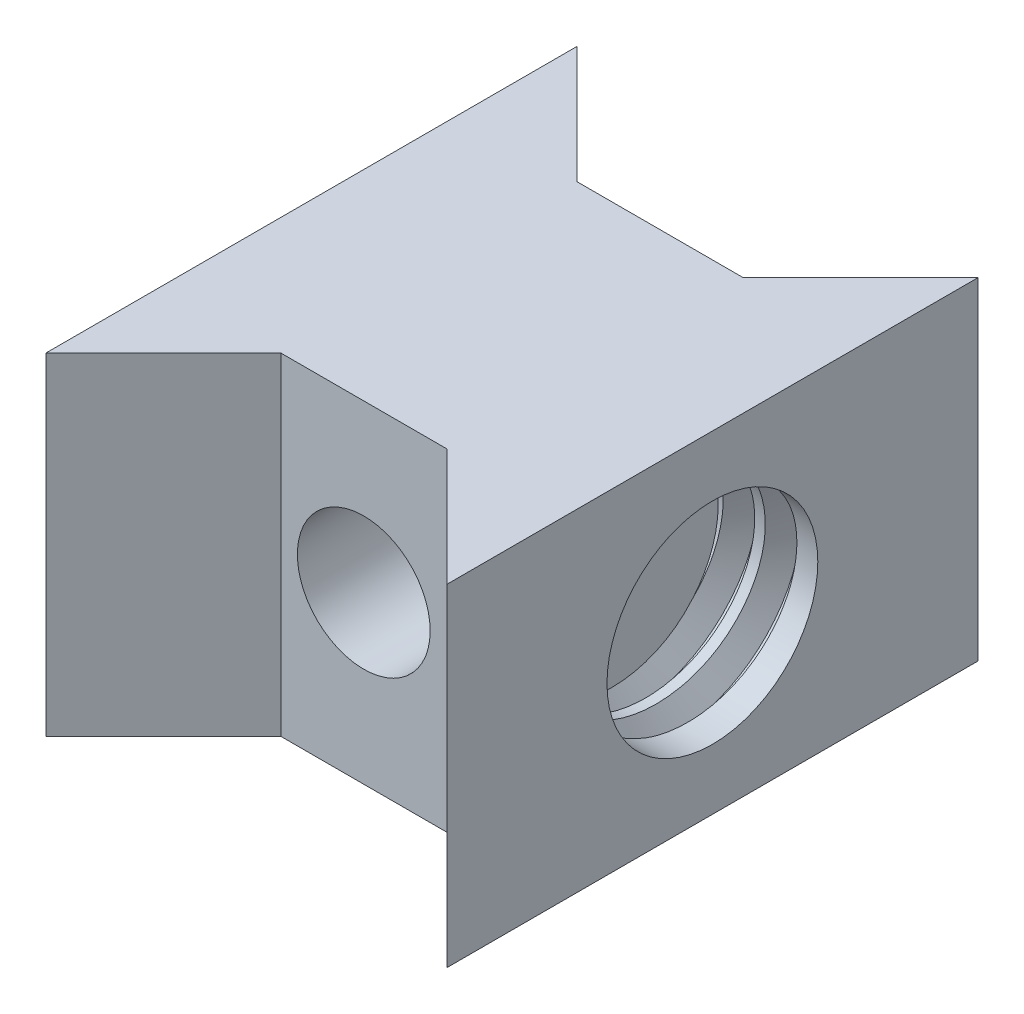
SolidWorks part; units mm, degrees
ref_plane "Front Plane" through (0, 0, 0) normal (0, 0, 1) x (1, 0, 0)
ref_plane "Top Plane" through (0, 0, 0) normal (0, 1, 0) x (1, 0, 0)
ref_plane "Right Plane" through (0, 0, 0) normal (1, 0, 0) x (0, 0, -1)
sketch "Sketch1" plane through (0, 0, 0) normal (0, 1, 0) x (1, 0, 0)
  line L0 (0, 0) -> (0, 8)
  line L1 (0, 0) -> (0, -8)
  line L2 (0, -8) -> (-3.5355, -4.4645)
  line L3 (0, 8) -> (-3.5355, 4.4645)
  line L5 (-3.5355, -4.4645) -> (-8.5355, -4.4645)
  line L6 (-3.5355, 4.4645) -> (-8.5355, 4.4645)
  line L7 (-8.5355, 4.4645) -> (-12.0711, 8)
  line L8 (-12.0711, 8) -> (-12.0711, -8)
  line L9 (-12.0711, -8) -> (-8.5355, -4.4645)
extrude "Boss-Extrude1" add sketch "Sketch1" along normal blind 10
sketch "Sketch3" plane through (0, 0, 0) normal (1, 0, 0) x (0, 0, -1)
  circle A0 centre (0, 5) radius 3.175
extrude "Cut-Extrude4" cut sketch "Sketch3" against normal blind 3
ref_plane "Plane4" through (-6.0355, 0, 0) normal (1, 0, 0) x (0, 0, -1)
mirror "Mirror2" about plane through (-6.0355, 0, 0) normal (1, 0, 0) of "Cut-Extrude4"
thread "Thread3" pitch 1.27 method cut profile "Thread Profile3" start angle 0, offset 0, length 3, pitch 1.27, diameter 6.35
ref_plane "Plane5" through (0, 5, 3.175) normal (0, -1, 0) x (0, 0, 1)
sketch "Thread Profile3" plane through (0, 5, 3.175) normal (0, -1, 0) x (0, 0, 1)
  line L0 (0, 0) -> (0, 1.27) construction
  line L1 (0, 0) -> (0.6874, 0.3969)
  line L2 (0.6874, 0.3969) -> (0.6874, 0.5556)
  line L3 (0.6874, 0.5556) -> (0, 0.9525)
  line L4 (0.6874, 0.4762) -> (0, 0.4762) construction
  line L11 (0, 0) -> (0, 0.9525)
  point P2 (0, 0)
  dimension "Pitch" = 1.27
  dimension "Profile_Angle" = 60
  dimension "Profile_Land" = 0.1588
  dimension "Profile_Height" = 0.6874
thread "Thread4" pitch 1.27 method cut profile "Thread Profile4" start angle 0, offset 0, length 3, pitch 1.27, diameter 6.35
ref_plane "Plane6" through (-12.0711, 5, -3.175) normal (0, -1, 0) x (0, 0, -1)
sketch "Thread Profile4" plane through (-12.0711, 5, -3.175) normal (0, -1, 0) x (0, 0, -1)
  line L0 (0, 0) -> (0, 1.27) construction
  line L1 (0, 0) -> (0.6874, 0.3969)
  line L2 (0.6874, 0.3969) -> (0.6874, 0.5556)
  line L3 (0.6874, 0.5556) -> (0, 0.9525)
  line L4 (0.6874, 0.4762) -> (0, 0.4762) construction
  line L11 (0, 0) -> (0, 0.9525)
  point P2 (0, 0)
  dimension "Pitch" = 1.27
  dimension "Profile_Angle" = 60
  dimension "Profile_Land" = 0.1588
  dimension "Profile_Height" = 0.6874
sketch "Sketch13" plane through (0, 0, 4.4645) normal (0, 0, 1) x (1, 0, 0)
  circle A0 centre (-6.0355, 5) radius 2
extrude "Cut-Extrude5" cut sketch "Sketch13" against normal through all
